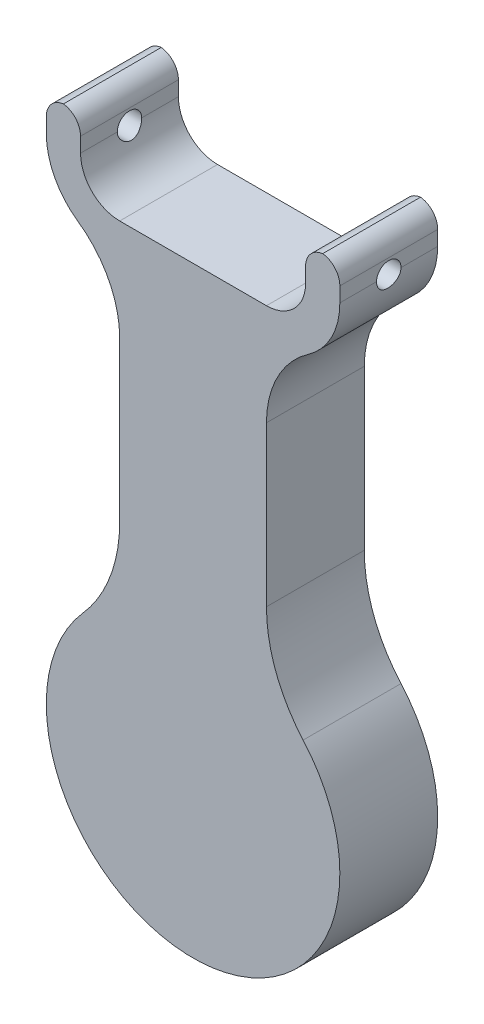
SolidWorks part; units mm, degrees
ref_plane "Front Plane" through (0, 0, 0) normal (0, 0, 1) x (1, 0, 0)
ref_plane "Top Plane" through (0, 0, 0) normal (0, 1, 0) x (1, 0, 0)
ref_plane "Right Plane" through (0, 0, 0) normal (1, 0, 0) x (0, 0, -1)
sketch "Sketch1" plane through (0, 0, 0) normal (0, 0, 1) x (1, 0, 0)
  circle A0 centre (0, 0) radius 15
  circle A1 centre (0, 0) radius 3
  dimension "D1" = 6
  dimension "D2" = 30
extrude "Boss-Extrude1" add sketch "Sketch1" along normal blind 10
sketch "Sketch2" plane through (0, 0, 0) normal (0, 0, 1) x (1, 0, 0)
  line L1 (-7.5, 12.9904) -> (7.5, 12.9904)
  line L2 (-7.5, 12.9904) -> (-7.5, 42.9904)
  line L3 (-7.5, 42.9904) -> (7.5, 42.9904)
  line L4 (7.5, 12.9904) -> (7.5, 42.9904)
  circle A0 centre (0, 0) radius 15 construction
  dimension "D1" = 15
  dimension "D2" = 30
extrude "Boss-Extrude2" add sketch "Sketch2" along normal up to surface (10 mm away) up to face at (15, 0, 10)
fillet "Fillet1" radius 15 2 edges at (-7.5, 12.9904, 5) (7.5, 12.9904, 5)
sketch "Sketch5" plane through (0, 0, 0) normal (0, 0, -1) x (-1, 0, 0)
  line L1 (-5, 3.5) -> (5, 3.5)
  line L2 (-5, 3.5) -> (-5, 1.5)
  line L3 (-5, 1.5) -> (5, 1.5)
  line L4 (5, 3.5) -> (5, 1.5)
  circle A0 centre (0, 0) radius 3 construction
  dimension "D1" = 1.5
  dimension "D2" = 2
  dimension "D3" = 10
  dimension "D4" = 5
extrude "Boss-Extrude3" add sketch "Sketch5" against normal blind 10
sketch "Sketch7" plane through (0, 0, 10) normal (0, 0, 1) x (1, 0, 0)
  circle A0 centre (0, 0) radius 3
extrude "Boss-Extrude4" add sketch "Sketch7" against normal blind 3
chamfer "Chamfer1" distance 0.7 angle 45 2 edges at (0, -3, 7) (0, 1.5, 7)
sketch "Sketch9" plane through (0, 0, 0) normal (0, 0, -1) x (-1, 0, 0)
  line L0 (-7.5, 42.9904) -> (7.5, 42.9904) construction
  line L1 (-7.5, 19.8431) -> (-7.5, 42.9904) construction
  line L3 (-15, 50.4904) -> (-15, 53.9904)
  line L4 (-15, 53.9904) -> (-11.5, 53.9904)
  line L5 (-11.5, 53.9904) -> (-11.5, 50.4904)
  line L6 (-7.5, 46.4904) -> (7.5, 46.4904)
  line L7 (0, 46.4904) -> (0, 42.9904)
  line L8 (7.5, 42.9904) -> (-7.5, 42.9904)
  line L9 (0, 62.4917) -> (0, 38.0275) construction
  line L10 (11.5, 53.9904) -> (11.5, 50.4904)
  line L11 (15, 53.9904) -> (11.5, 53.9904)
  line L12 (15, 50.4904) -> (15, 53.9904)
  arc A0 (-15, 50.4904) -> (-7.5, 42.9904) centre (-7.5, 50.4904) ccw
  arc A2 (-11.5, 50.4904) -> (-7.5, 46.4904) centre (-7.5, 50.4904) ccw
  arc A3 (11.5, 50.4904) -> (7.5, 46.4904) centre (7.5, 50.4904) cw
  arc A4 (15, 50.4904) -> (7.5, 42.9904) centre (7.5, 50.4904) cw
  line M23 (7.5, 42.9904) -> (-7.5, 42.9904)
  dimension "D1" = 3.5
  dimension "12.5" = 15
  dimension "D2" = 7.5
  dimension "D3" = 0
  dimension "D7" = 3.5
  dimension "D8" = 0
extrude "Boss-Extrude6" add sketch "Sketch9" against normal blind 10 contours A2 L5 L4 L3 A0 L7 L6 M23 | A4 L12 L11 L10 A3 L6 L7 M23 region at (14.814, 52.2404, 0) region at (-0.186, 44.7404, 0)
fillet "Fillet4" radius 2 4 edges at (11.5, 53.9904, 5) (15, 53.9904, 5) (-11.5, 53.9904, 5) (-15, 53.9904, 5)
fillet "Fillet2" radius 10 2 edges at (-7.5, 42.9904, 5) (7.5, 42.9904, 5)
sketch "Sketch10" plane through (15, 0, 0) normal (1, 0, 0) x (0, 0, -1)
  line L0 (-10, 50.4904) -> (0, 50.4904) construction
  line L1 (0, 44.3355) -> (0, 50.4904) construction
  circle A0 centre (-5, 50.4904) radius 1.25
  dimension "D3" = 2.5
  dimension "D1" = 0
  dimension "D2" = 5
extrude "Cut-Extrude1" cut sketch "Sketch10" against normal through all both and the other way through all
